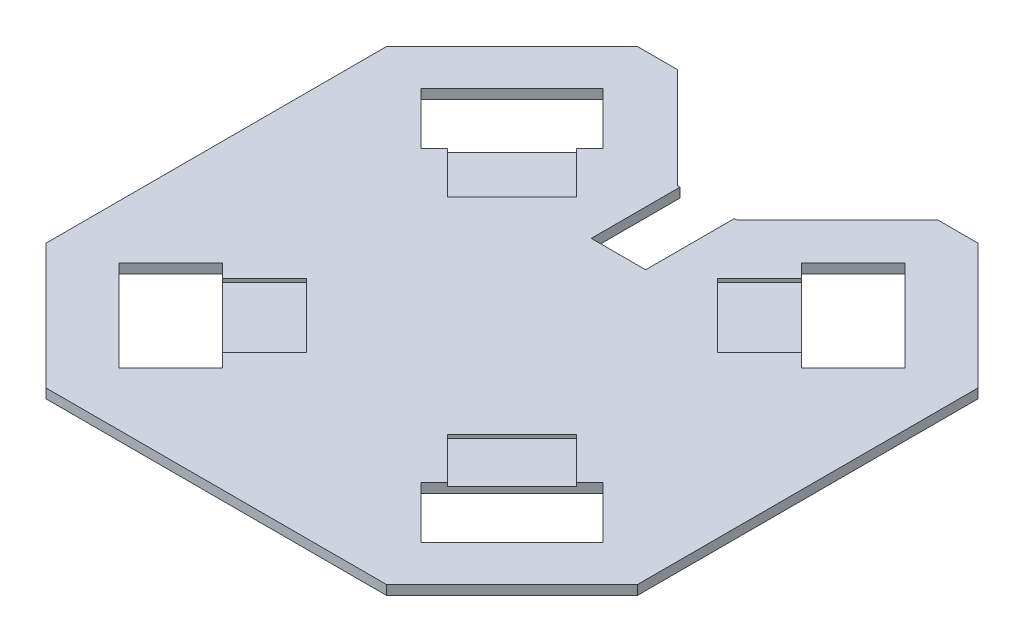
SolidWorks part; units mm, degrees
material "1060 合金"
ref_plane "前视基准面" through (0, 0, 0) normal (0, 0, 1) x (1, 0, 0)
ref_plane "上视基准面" through (0, 0, 0) normal (0, 1, 0) x (1, 0, 0)
ref_plane "右视基准面" through (0, 0, 0) normal (1, 0, 0) x (0, 0, -1)
ref_axis "中轴" through (0, -11.5924, 0) along (0, 1, 0)
sketch "草图1" plane through (0, 0, 0) normal (0, 1, 0) x (1, 0, 0)
  line L1 (-250, -250) -> (250, -250)
  line L2 (-250, -250) -> (-250, 250)
  line L3 (-250, 250) -> (250, 250)
  line L4 (250, -250) -> (250, 250)
  line L5 (-250, -250) -> (250, 250) construction
  line L6 (-250, 250) -> (250, -250) construction
  point P0 (0, 0)
  dimension "D1" = 500
  dimension "D2" = 500
extrude "凸台-拉伸1" add sketch "草图1" along normal mid plane 8
sketch3d "3D草图8"
  circle A0 centre (0, 0, -284) radius 65.3299
  circle A1 centre (0, 0, -284) radius 65.3299
  circle A2 centre (0, 0, -250) radius 65.3299
  circle A3 centre (0, 0, -250) radius 65.3299
  point P2 (0, -65.3299, -284)
  point P4 (0, -65.3299, -284)
  point P7 (0, -65.3299, -250)
  point P9 (0, -65.3299, -250)
sketch "草图3" plane through (0, 4, 0) normal (0, 1, 0) x (1, 0, 0)
  line L0 (250, 250) -> (-250, 250) construction
  line L1 (250, 250) -> (-250, 250) construction
  line L2 (0, 0) -> (0, 283.6146) construction
  line L3 (110, 250) -> (25, 165)
  line L4 (25, 165) -> (-25, 165)
  line L5 (-110, 250) -> (-25, 165)
  point P10 (0, 165)
  dimension "D1" = 45
  dimension "D2" = 85
  dimension "D3" = 220
extrude "进球口" cut sketch "草图3" against normal through all and the other way through all
sketch "草图5" plane through (0, 4, 0) normal (0, 1, 0) x (1, 0, 0)
  line L0 (250, 250) -> (110, 250) construction
  line L1 (0, 0) -> (0, 372.053) construction
  line L3 (-23, 250) -> (23, 250)
  line L4 (-23, 250) -> (-23, 90)
  line L5 (-23, 90) -> (23, 90)
  line L6 (23, 250) -> (23, 90)
  line L7 (-23, 250) -> (23, 90) construction
  line L8 (-23, 90) -> (23, 250) construction
  point P7 (0, 170)
  dimension "D1" = 90
  dimension "D2" = 46
extrude "射门槽" cut sketch "草图5" against normal through all
sketch3d "轮系相交面"
  line L0 (89.4937, 4, 159.4079) -> (127.6774, 4, 197.5917)
  line L1 (197.5917, 4, 127.6774) -> (159.4079, 4, 89.4937)
  line L2 (197.5917, 4, 127.6774) -> (159.4079, 4, 89.4937) construction
  line L3 (89.4937, 4, 159.4079) -> (127.6774, 4, 197.5917) construction
  line L4 (197.5917, 4, 127.6774) -> (127.6774, 4, 197.5917)
  line L5 (197.5917, 4, 127.6774) -> (127.6774, 4, 197.5917) construction
  line L6 (159.4079, 4, 89.4937) -> (89.4937, 4, 159.4079)
  line L7 (159.4079, 4, 89.4937) -> (89.4937, 4, 159.4079) construction
sketch3d "安装面"
  line L0 (59.7505, 4, 114.1977) -> (95.1059, 4, 149.5531)
  line L1 (59.7505, 4, 114.1977) -> (95.1059, 4, 149.5531)
  line L2 (149.5531, 4, 95.1059) -> (114.1977, 4, 59.7505)
  line L3 (149.5531, 4, 95.1059) -> (114.1977, 4, 59.7505)
sketch "草图4" plane through (0, 4, 0) normal (0, 1, 0) x (1, 0, 0)
  line L0 (83.8368, -160.8221) -> (160.8221, -83.8368)
  line L1 (160.8221, -83.8368) -> (204.6627, -127.6774)
  line L2 (204.6627, -127.6774) -> (127.6774, -204.6627)
  line L3 (127.6774, -204.6627) -> (83.8368, -160.8221)
  line L4 (159.4079, -89.4937) -> (89.4937, -159.4079) construction
  line L5 (0, 0) -> (0, 366.7415) construction
  line L6 (0, 0) -> (230.8457, -230.8457) construction
  line L8 (197.5917, -127.6774) -> (159.4079, -89.4937) construction
  line L9 (197.5917, -127.6774) -> (127.6774, -197.5917) construction
  dimension "D1" = 3
  dimension "D2" = 45
  dimension "D3" = 5
  dimension "D4" = 5
extrude "轮孔" cut sketch "草图4" against normal through all
sketch "草图7" plane through (0, 4, 0) normal (0, 1, 0) x (1, 0, 0)
  line L0 (95.1059, -149.5531) -> (59.7505, -114.1977)
  line L1 (59.7505, -114.1977) -> (114.1977, -59.7505)
  line L2 (114.1977, -59.7505) -> (149.5531, -95.1059)
  line L3 (149.5531, -95.1059) -> (95.1059, -149.5531)
  line L4 (0, 0) -> (166.1701, -166.1701) construction
  line L5 (127.6774, -204.6627) -> (204.6627, -127.6774) construction
  dimension "D1" = 50
  dimension "D2" = 77
extrude "安装槽" cut sketch "草图7" against normal blind 3
pattern_circular "阵列(圆周)1" count 4 over 360 about axis through (0, -11.5924, 0) along (0, 1, 0) of "轮孔", "安装槽"
chamfer "倒角1" distance 106 angle 45 4 edges at (250, 0, -250) (250, 0, 250) (-250, 0, 250) (-250, 0, -250)
